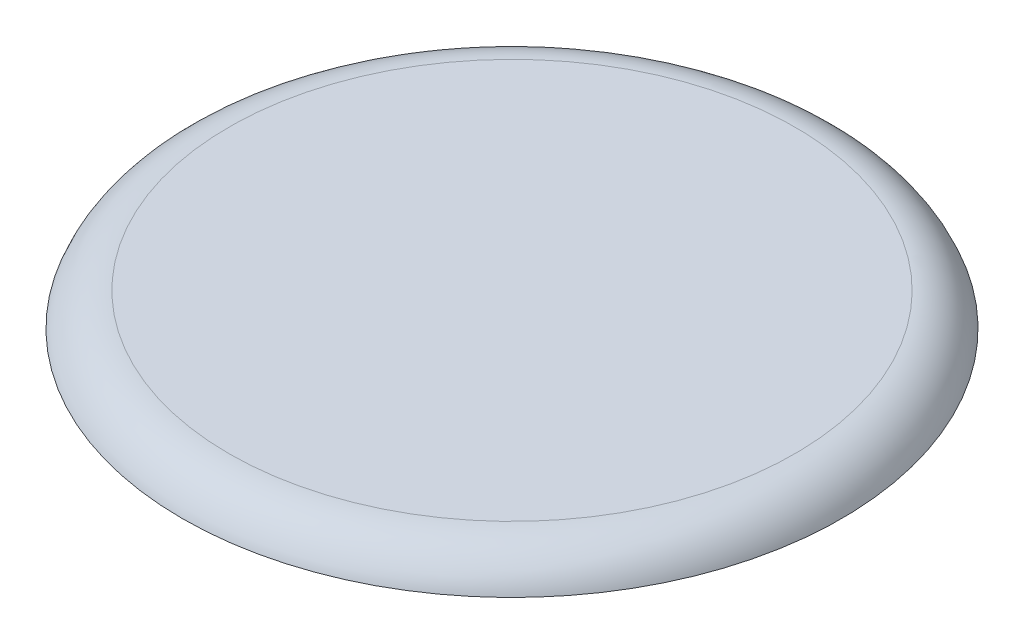
SolidWorks part; units mm, degrees
other "DetailItem1"
material "ABS"
ref_plane "Front Plane" through (0, 0, 0) normal (0, 0, 1) x (1, 0, 0)
ref_plane "Top Plane" through (0, 0, 0) normal (0, 1, 0) x (1, 0, 0)
ref_plane "Right Plane" through (0, 0, 0) normal (1, 0, 0) x (0, 0, -1)
sketch "Sketch2" plane through (0, 0, 0) normal (0, 1, 0) x (1, 0, 0)
  circle A0 centre (0, 0) radius 127
  dimension "D1" = 254
extrude "Boss-Extrude1" add sketch "Sketch2" along normal blind 12.7
fillet "Fillet1" radius 19.05 1 edges at (0, 12.7, 127)
sketch "Sketch3" plane through (0, 0, 0) normal (0, -1, 0) x (1, 0, 0)
  circle A0 centre (0, 0) radius 111.125
  dimension "D1" = 222.25
extrude "Cut-Extrude1" cut sketch "Sketch3" against normal blind 2.54
